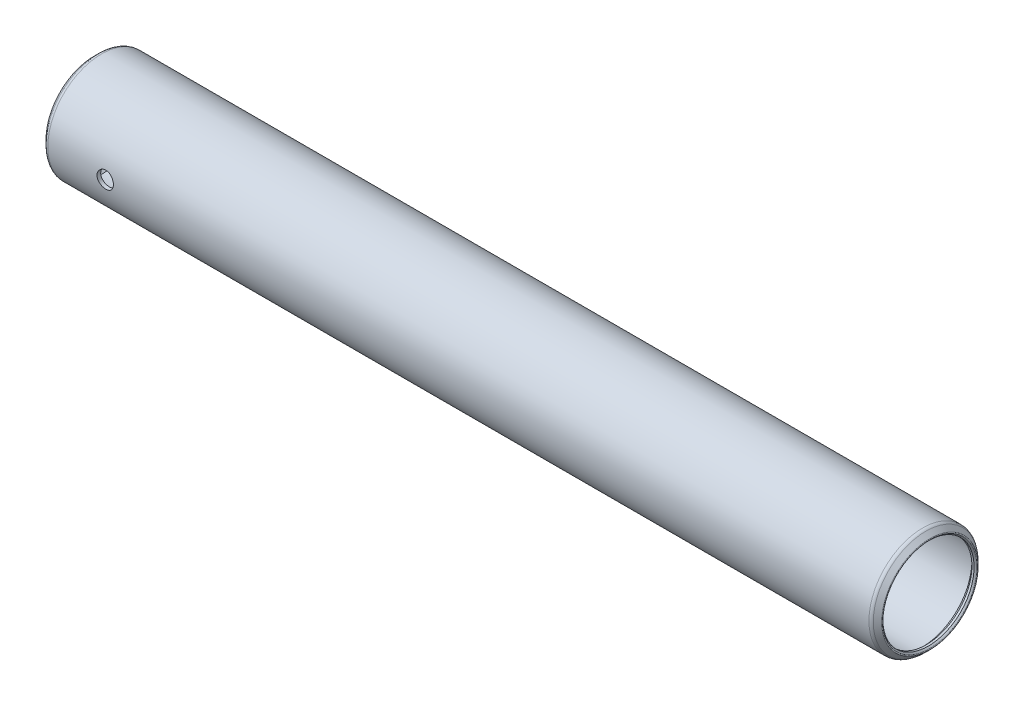
SolidWorks part; units mm, degrees
material "Cast Alloy Steel"
ref_plane "Front Plane" through (0, 0, 0) normal (0, 0, 1) x (1, 0, 0)
ref_plane "Top Plane" through (0, 0, 0) normal (0, 1, 0) x (1, 0, 0)
ref_plane "Right Plane" through (0, 0, 0) normal (1, 0, 0) x (0, 0, -1)
ref_plane "Plane1" through (120.5484, 0, 0) normal (1, 0, 0) x (0, 0, -1)
sketch "Sketch1" plane through (0, 0, 0) normal (0, 0, 1) x (1, 0, 0)
  line L0 (-0.518, 6.8362) -> (-0.3175, 6.6357)
  line L1 (-0.3175, 6.6357) -> (0, 6.6357)
  line L2 (0, 6.6357) -> (0.635, 7.2707)
  line L3 (0.635, 7.2707) -> (119.9134, 7.2707)
  line L4 (119.9134, 7.2707) -> (120.5484, 6.6357)
  line L5 (120.5484, 6.6357) -> (120.8659, 6.6357)
  line L6 (120.8659, 6.6357) -> (121.0664, 6.8362)
  line L7 (121.0664, 7.0158) -> (120.4577, 7.6245)
  line L8 (120.0087, 7.8105) -> (0.5398, 7.8105)
  line L9 (0.0907, 7.6245) -> (-0.518, 7.0158)
  line L10 (120.5484, 0) -> (0, 0) construction
  arc A0 (-0.518, 7.0158) -> (-0.518, 6.8362) centre (-0.4282, 6.926) ccw
  arc A1 (121.0664, 6.8362) -> (121.0664, 7.0158) centre (120.9766, 6.926) ccw
  arc A2 (120.4577, 7.6245) -> (120.0087, 7.8105) centre (120.0086, 7.1755) ccw
  arc A3 (0.5398, 7.8105) -> (0.0907, 7.6245) centre (0.5397, 7.1755) ccw
revolve "Revolve1" add sketch "Sketch1" angle 360 about L10 reverse direction yes
sketch "Sketch2" plane through (0, 0, 0) normal (0, 0, 1) x (1, 0, 0)
  circle A0 centre (8.89, 0) radius 1.1938
extrude "Cut-Extrude1" cut sketch "Sketch2" along normal blind 7.8105
ref_plane "Plane2" through (60.2742, 0, 0) normal (1, 0, 0) x (0, 0, -1)
ref_plane "cp1 XY" through (60.2742, 0, 0) normal (1, 0, 0) x (0, 0, -1)
ref_plane "cp1 XZ" through (0, 7.8105, 0) normal (0, -1, 0) x (-1, 0, 0)
ref_plane "cp1 YZ" through (0, 0, 0) normal (0, 0, -1) x (-1, 0, 0)
ref_axis "cp1 X" through (60.2742, 7.8105, 80.9) along (0, 0, -1)
ref_axis "cp1 Y" through (60.2742, -50, 0) along (0, 1, 0)
ref_axis "cp1 Z" through (80.9, 7.8105, 0) along (-1, 0, 0)
sketch3d "cp1"
  point P0 (60.2742, 7.8105, 0)
ref_plane "cp2 XY" through (60.2742, 0, 0) normal (1, 0, 0) x (0, 0, -1)
ref_plane "cp2 XZ" through (0, 0, 0) normal (0, -1, 0) x (-1, 0, 0)
ref_plane "cp2 YZ" through (0, 0, -7.8105) normal (0, 0, -1) x (-1, 0, 0)
ref_axis "cp2 X" through (60.2742, 0, 80.9) along (0, 0, -1)
ref_axis "cp2 Y" through (60.2742, -50, -7.8105) along (0, 1, 0)
ref_axis "cp2 Z" through (80.9, 0, -7.8105) along (-1, 0, 0)
sketch3d "cp2"
  point P0 (60.2742, 0, -7.8105)
ref_plane "cp3 XY" through (60.2742, 0, 0) normal (1, 0, 0) x (0, 0, -1)
ref_plane "cp3 XZ" through (0, -7.8105, 0) normal (0, -1, 0) x (-1, 0, 0)
ref_plane "cp3 YZ" through (0, 0, 0) normal (0, 0, -1) x (-1, 0, 0)
ref_axis "cp3 X" through (60.2742, -7.8105, 80.9) along (0, 0, -1)
ref_axis "cp3 Y" through (60.2742, -50, 0) along (0, 1, 0)
ref_axis "cp3 Z" through (80.9, -7.8105, 0) along (-1, 0, 0)
sketch3d "cp3"
  point P0 (60.2742, -7.8105, 0)
ref_plane "cp4 XY" through (60.2742, 0, 0) normal (1, 0, 0) x (0, 0, -1)
ref_plane "cp4 XZ" through (0, 0, 0) normal (0, -1, 0) x (-1, 0, 0)
ref_plane "cp4 YZ" through (0, 0, 7.8105) normal (0, 0, -1) x (-1, 0, 0)
ref_axis "cp4 X" through (60.2742, 0, 80.9) along (0, 0, -1)
ref_axis "cp4 Y" through (60.2742, -50, 7.8105) along (0, 1, 0)
ref_axis "cp4 Z" through (80.9, 0, 7.8105) along (-1, 0, 0)
sketch3d "cp4"
  point P0 (60.2742, 0, 7.8105)
ref_plane "tube_front XY" through (0, 0, 0) normal (1, 0, 0) x (0, 0, -1)
ref_plane "tube_front XZ" through (0, 0, 0) normal (0, -1, 0) x (-1, 0, 0)
ref_plane "tube_front YZ" through (0, 0, 0) normal (0, 0, -1) x (-1, 0, 0)
ref_axis "tube_front X" through (0, 0, 80.9) along (0, 0, -1)
ref_axis "tube_front Y" through (0, -50, 0) along (0, 1, 0)
ref_axis "tube_front Z" through (80.9, 0, 0) along (-1, 0, 0)
sketch3d "tube_front"
  point P0 (0, 0, 0)
ref_plane "tube_rear XY" through (120.5484, 0, 0) normal (1, 0, 0) x (0, 0, -1)
ref_plane "tube_rear XZ" through (0, 0, 0) normal (0, -1, 0) x (-1, 0, 0)
ref_plane "tube_rear YZ" through (0, 0, 0) normal (0, 0, -1) x (-1, 0, 0)
ref_axis "tube_rear X" through (120.5484, 0, 80.9) along (0, 0, -1)
ref_axis "tube_rear Y" through (120.5484, -50, 0) along (0, 1, 0)
ref_axis "tube_rear Z" through (80.9, 0, 0) along (-1, 0, 0)
sketch3d "tube_rear"
  point P0 (120.5484, 0, 0)
